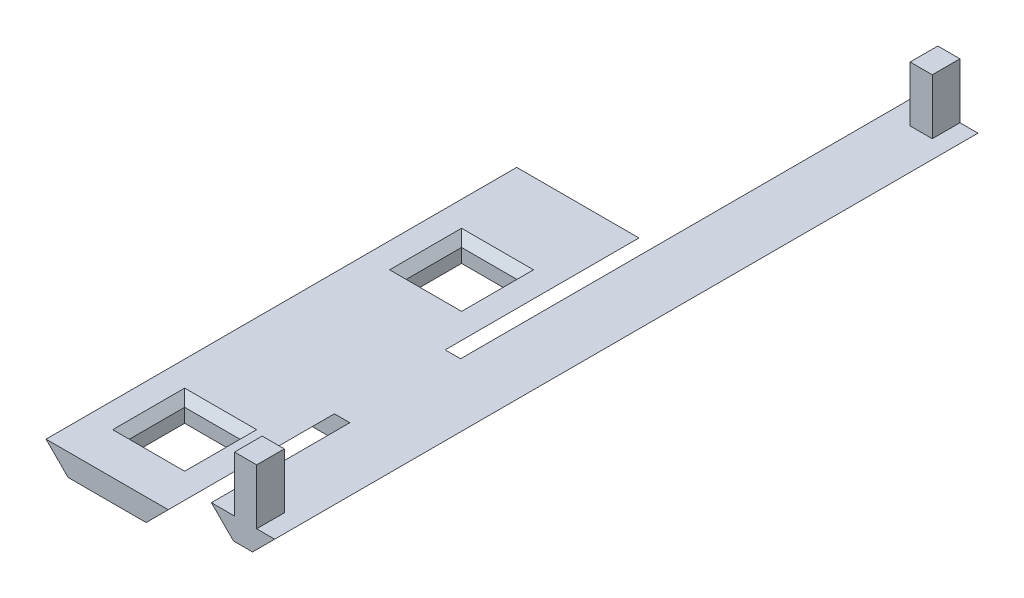
SolidWorks part; units mm, degrees
note: The reader was unsure of these and kept them because the rebuilt part matched: shared geometry of "Szkic1<4>".
ref_plane "Płaszczyzna przednia" through (0, 0, 0) normal (0, 0, 1) x (1, 0, 0)
ref_plane "Płaszczyzna górna" through (0, 0, 0) normal (0, 1, 0) x (1, 0, 0)
ref_plane "Płaszczyzna prawa" through (0, 0, 0) normal (1, 0, 0) x (0, 0, -1)
sketch "Szkic1" plane through (0, 0, 0) normal (0, 0, 1) x (1, 0, 0)
  line L0 (7.5, 0) -> (-7.5, 0)
  line L1 (-7.5, 0) -> (-11.5, 4)
  line L2 (-11.5, 4) -> (11.5, 4)
  line L3 (0, 0) -> (0, 34.0436) construction
  line L4 (7.5, 0) -> (11.5, 4)
  line L5 (-10.5787, 4) -> (-6.5787, 0)
  line L6 (10.5787, 4) -> (6.5787, 0)
  line L7 (18, 0) -> (22, 0)
  line L8 (14, 4) -> (26, 4)
  line L9 (26, 4) -> (22, 0)
  line L10 (18, 0) -> (14, 4)
  line L11 (20, 4) -> (20, 0) construction
  line L12 (14.2828, 4) -> (18.2828, 0)
  line L13 (25.7172, 4) -> (21.7172, 0)
  point P7 (0, 4)
  dimension "D1" = 45
  dimension "D2" = 15
  dimension "D3" = 4
  dimension "D4" = 0.6515
  dimension "D5" = 45
  dimension "D6" = 45
  dimension "D7" = 4
  dimension "D8" = 20
  dimension "D9" = 0.2
extrude "Dodanie-wyciągnięcie1" add sketch "Szkic1" along normal blind 85 contours L0 L3 L2 L5 | L3 L0 L6 L2
sketch "Szkic2" plane through (0, 0, 0) normal (0, -1, 0) x (1, 0, 0)
  line L0 (0.4607, 85) -> (0.4607, 0) construction
  line L1 (7.5, 85) -> (-6.5787, 85) construction
  line L3 (-4.5393, 26) -> (5.4607, 26)
  line L4 (-4.5393, 26) -> (-4.5393, 16)
  line L5 (-4.5393, 16) -> (5.4607, 16)
  line L6 (5.4607, 26) -> (5.4607, 16)
  line L7 (-4.5393, 26) -> (5.4607, 16) construction
  line L8 (-4.5393, 16) -> (5.4607, 26) construction
  line L9 (7.5, 0) -> (-6.5787, 0) construction
  line L11 (-4.5393, 76) -> (5.4607, 76)
  line L12 (-4.5393, 76) -> (-4.5393, 66)
  line L13 (-4.5393, 66) -> (5.4607, 66)
  line L14 (5.4607, 76) -> (5.4607, 66)
  line L15 (-4.5393, 76) -> (5.4607, 66) construction
  line L16 (-4.5393, 66) -> (5.4607, 76) construction
  point P4 (0.4607, 21)
  point P11 (0.4607, 71)
  dimension "D1" = 10
  dimension "D2" = 16
  dimension "D3" = 50
extrude "Wytnij-wyciągnięcie1" cut sketch "Szkic2" against normal blind 80
extrude "Dodanie-wyciągnięcie3" add sketch "Szkic1<4>" along normal blind 80 and the other way blind 47 separate body contours L13 L8 L12 L7
sketch "Szkic1<4>" plane through (0, 0, 0) normal (0, 0, 1) x (1, 0, 0) same geometry as "Szkic1"
sketch "Szkic4" plane through (0, 0, 0) normal (0, -1, 0) x (1, 0, 0)
  line L0 (7.5, 85) -> (7.5, 0) construction
  line L1 (7.5, 55) -> (18.2828, 55)
  line L2 (7.5, 55) -> (7.5, 35)
  line L3 (7.5, 35) -> (18.2828, 35)
  line L4 (18.2828, 55) -> (18.2828, 35)
  line L5 (18.2828, -47) -> (18.2828, 80) construction
  line L6 (7.5, 35) -> (7.5, 0) construction
  line L7 (7.5, 0) -> (11.5, 0) construction
  line L8 (12.8914, 35) -> (12.8914, 12) construction
  dimension "D1" = 20
  dimension "D2" = 35
  dimension "D3" = 23
extrude "Dodanie-wyciągnięcie4" add sketch "Szkic4" against normal up to vertex (4 mm away)
sketch "Szkic5" plane through (0, 4, 0) normal (0, 1, 0) x (1, 0, 0)
  line L0 (14.2828, -80) -> (25.7172, -80) construction
  line L1 (18.4607, -80) -> (22.4607, -80)
  line L2 (18.4607, -80) -> (18.4607, -75)
  line L3 (18.4607, -75) -> (22.4607, -75)
  line L4 (22.4607, -80) -> (22.4607, -75)
  line L6 (14.2828, -80) -> (25.7172, -80)
  line L7 (20.4607, -80) -> (20, -80) construction
  line M9 (14.2828, -80) -> (25.7172, -80)
  dimension "D1" = 4
  dimension "D2" = 5
  dimension "D3" = 0.4607
extrude "Dodanie-wyciągnięcie5" add sketch "Szkic5" along normal blind 10 contours L6 L4 L3 L2 M9
sketch "Szkic6" plane through (0, 4, 0) normal (0, 1, 0) x (1, 0, 0)
  line L0 (20.4607, -80) -> (20.4607, 47) construction
  line L1 (18.4607, -80) -> (22.4607, -80) construction
  line L2 (14.2828, 47) -> (25.7172, 47) construction
  line L3 (18.4607, 42) -> (18.4607, -75) construction
  line L4 (22.4607, 42) -> (18.4607, 42)
  line L5 (22.4607, 42) -> (22.4607, 47)
  line L6 (22.4607, 47) -> (18.4607, 47)
  line L7 (18.4607, 42) -> (18.4607, 47)
  line L8 (22.4607, 42) -> (18.4607, 47) construction
  line L9 (22.4607, 47) -> (18.4607, 42) construction
  point P6 (20.4607, 44.5)
  dimension "D1" = 5
extrude "Dodanie-wyciągnięcie6" add sketch "Szkic6" along normal up to vertex (10 mm away) up to point (22.4606, 14, 75)
chamfer "Sfazowanie1" distance 1.5 angle 45 8 edges at (5.4607, 4, 21) (0.4607, 4, 16) (-4.5393, 4, 21) (0.4607, 4, 26) (0.4607, 4, 66) (5.4607, 4, 71) (0.4607, 4, 76) (-4.5393, 4, 71)
